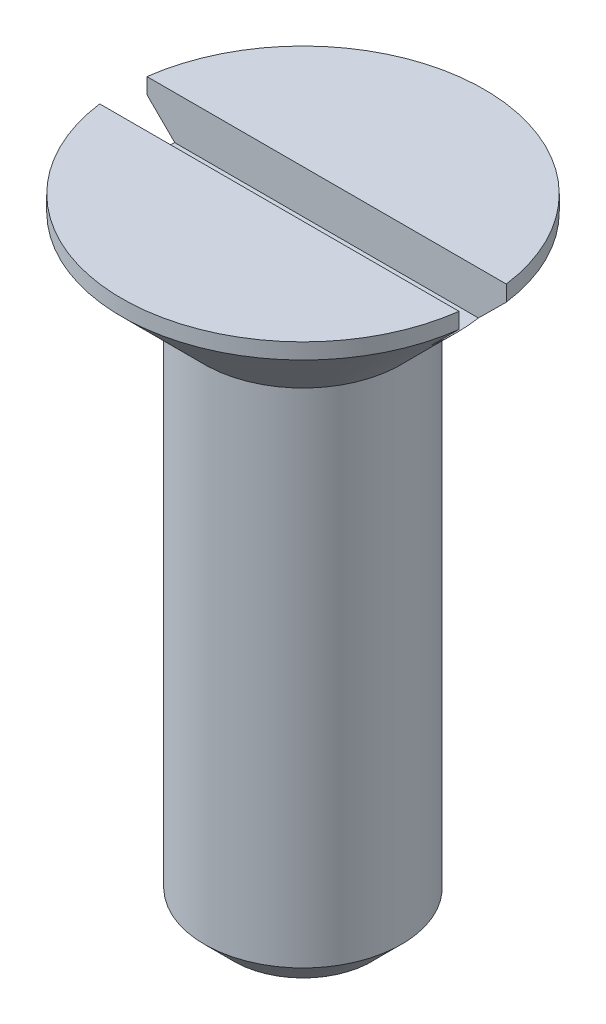
SolidWorks part; units mm, degrees
ref_plane "Спереди" through (0, 0, 0) normal (0, 0, 1) x (1, 0, 0)
ref_plane "Сверху" through (0, 0, 0) normal (0, 1, 0) x (1, 0, 0)
ref_plane "Справа" through (0, 0, 0) normal (1, 0, 0) x (0, 0, -1)
sketch "Эскиз1" plane through (0, 0, 0) normal (0, 0, 1) x (1, 0, 0)
  line L0 (0, 125.7632) -> (0, 0) construction
  line L2 (0, 16) -> (0, 0)
  line L3 (0, 16) -> (4.6, 16)
  line L4 (2.5, 13.5) -> (2.5, 0)
  line L5 (2.5, 13.5) -> (4.6, 15.6)
  line L6 (2.5, 0) -> (0, 0)
  line L7 (4.6, 16) -> (4.6, 15.6)
  dimension "D1" = 4.6
  dimension "D2" = 16
  dimension "D3" = 2.5
  dimension "D4" = 45
  dimension "D5" = 2.5
revolve "Повернуть1" add sketch "Эскиз1" angle 360 about L0
ref_axis "Ось4" through (0, 18.7854, 0) along (0, -1, 0)
sketch "Эскиз13" plane through (0, 16, 0) normal (0, 1, 0) x (-1, 0, 0)
  line L1 (4.6, -0.6) -> (-4.6, -0.6)
  line L2 (4.6, -0.6) -> (4.6, 0.6)
  line L3 (4.6, 0.6) -> (-4.6, 0.6)
  line L4 (-4.6, -0.6) -> (-4.6, 0.6)
  dimension "D1" = 4.6
  dimension "D2" = 9.2
  dimension "D3" = 0.6
  dimension "D4" = 1.2
extrude "Вырез-Вытянуть9" cut sketch "Эскиз13" against normal blind 1.1
chamfer "Фаска1" distance 0.75 angle 45 1 edges at (-2.5, 0, 0)
